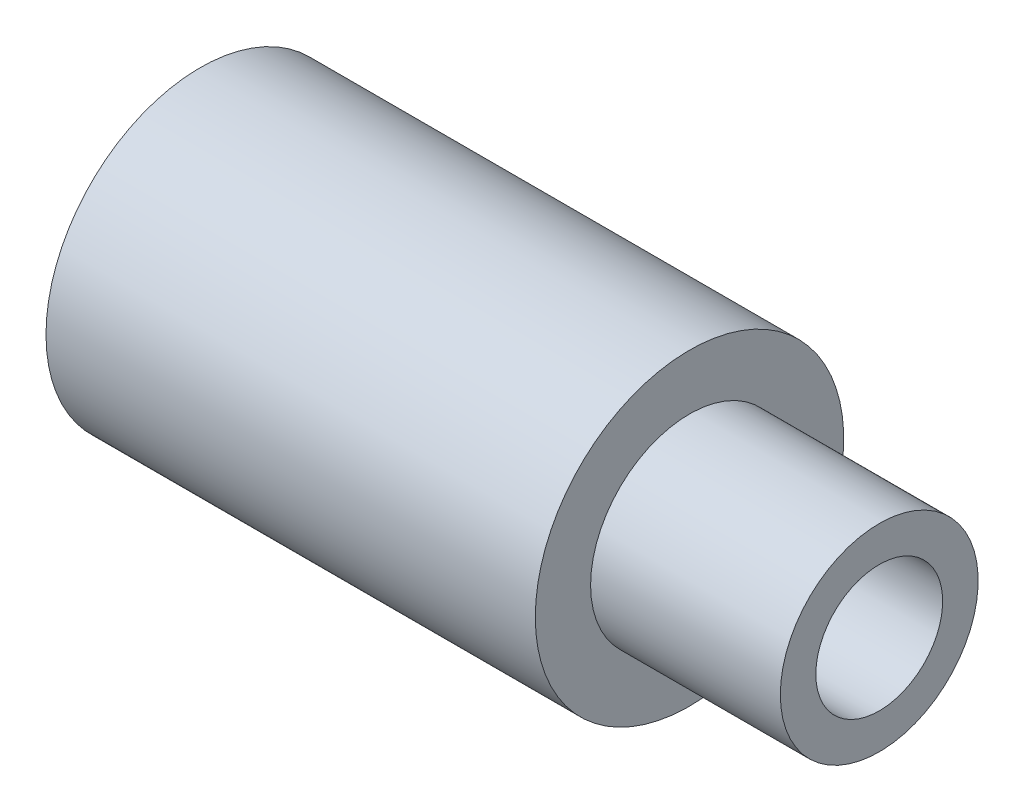
SolidWorks part; units mm, degrees
ref_plane "Front Plane" through (0, 0, 0) normal (0, 0, 1) x (1, 0, 0)
ref_plane "Top Plane" through (0, 0, 0) normal (0, 1, 0) x (1, 0, 0)
ref_plane "Right Plane" through (0, 0, 0) normal (1, 0, 0) x (0, 0, -1)
sketch "Conn_T4_ORB4_Bored Sketch" plane through (0, 0, 0) normal (0, 0, 1) x (1, 0, 0)
  line L0 (-1000, 0) -> (1000, 0) construction
  line L1 (9.5, 0) -> (9.5, 4.953)
  line L2 (9.5, 4.953) -> (0, 4.953)
  line L3 (0, 4.953) -> (0, 7.722)
  line L4 (0, 7.722) -> (-24.5, 7.722)
  line L5 (-24.5, 7.722) -> (-24.5, 0)
  line L6 (-24.5, 0) -> (9.5, 0)
revolve "Conn_T4_ORB4_Bored" add sketch "Conn_T4_ORB4_Bored Sketch" angle 360 about L0
ref_axis "Engine Axis" through (11.2, 0, 0) along (-1, 0, 0)
sketch "Socket Sketch" plane through (0, 0, 0) normal (0, 0, 1) x (1, 0, 0)
  line L0 (-1000, 0) -> (1000, 0) construction
  line L1 (-25.5, 0) -> (-25.5, 3.175)
  line L2 (-25.5, 3.175) -> (10.5, 3.175)
  line L3 (10.5, 3.175) -> (10.5, 0)
  line L4 (10.5, 0) -> (-25.5, 0)
revolve "Socket" cut sketch "Socket Sketch" angle 360 about L0
